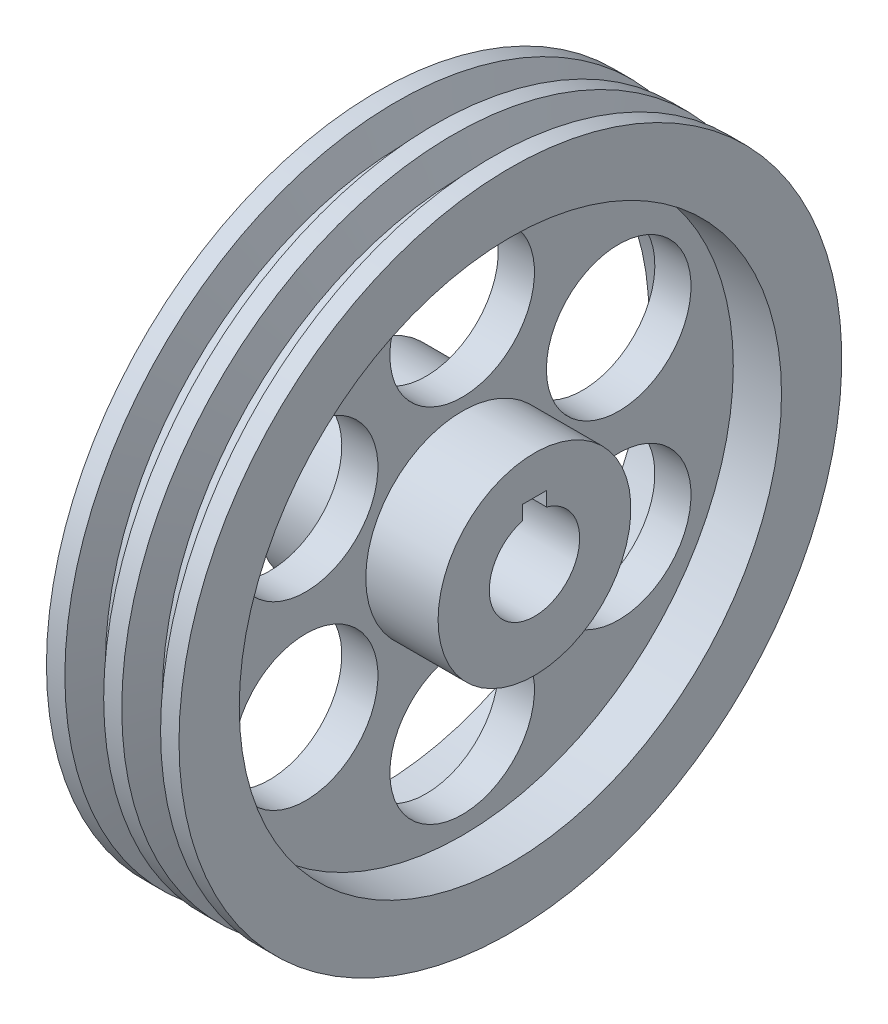
SolidWorks part; units mm, degrees
ref_plane "前视基准面" through (0, 0, 0) normal (0, 0, 1) x (1, 0, 0)
ref_plane "上视基准面" through (0, 0, 0) normal (0, 1, 0) x (1, 0, 0)
ref_plane "右视基准面" through (0, 0, 0) normal (1, 0, 0) x (0, 0, -1)
other "Configuration Table"
sketch "草图5" plane through (0, 0, 0) normal (0, 0, 1) x (1, 0, 0)
  line L0 (-49.9228, 0) -> (64.5367, 0) construction
  line L1 (-15.9481, 7.5) -> (14.0519, 7.5)
  line L2 (14.0519, 7.5) -> (14.0519, 16)
  line L3 (14.0519, 16) -> (2.0519, 16)
  line L4 (2.0519, 16) -> (2.0519, 45)
  line L5 (2.0519, 45) -> (10.0519, 45)
  line L6 (10.0519, 45) -> (10.0519, 55)
  line L7 (10.0519, 55) -> (6.9951, 55)
  line L8 (6.9951, 55) -> (5.2735, 50)
  line L9 (5.2735, 50) -> (2.2735, 50)
  line L10 (2.2735, 50) -> (0.5519, 55)
  line L11 (0.5519, 55) -> (-2.4481, 55)
  line L12 (-0.9481, 55) -> (-0.9481, 7.5) construction
  line L13 (-4.1698, 50) -> (-2.4481, 55)
  line L14 (-7.1698, 50) -> (-4.1698, 50)
  line L15 (-8.8914, 55) -> (-7.1698, 50)
  line L16 (-11.9481, 55) -> (-8.8914, 55)
  line L17 (-11.9481, 45) -> (-11.9481, 55)
  line L18 (-3.9481, 45) -> (-11.9481, 45)
  line L19 (-3.9481, 16) -> (-3.9481, 45)
  line L20 (-15.9481, 16) -> (-3.9481, 16)
  line L21 (-15.9481, 7.5) -> (-15.9481, 16)
  line L22 (3.7735, 50) -> (3.7735, 48.9551) construction
  line L23 (0, 0) -> (0, 7.5) construction
  dimension "D1" = 30
  dimension "D3" = 38
  dimension "D4" = 6
  dimension "D5" = 22
  dimension "D6" = 3
  dimension "D7" = 55
  dimension "D8" = 50
  dimension "D9" = 45
  dimension "D10" = 7.5
  dimension "D11" = 16
  dimension "D12" = 0.9481
revolve "旋转4" add sketch "草图5" angle 360 about L0
sketch "草图6" plane through (14.0519, 0, 0) normal (1, 0, 0) x (0, 0, -1)
  line L1 (-2, 9.6) -> (2, 9.6)
  line L2 (-2, 9.6) -> (-2, 0)
  line L3 (-2, 0) -> (2, 0)
  line L4 (2, 9.6) -> (2, 0)
  line L5 (-2, 9.6) -> (2, 0) construction
  line L6 (-2, 0) -> (2, 9.6) construction
  point P0 (0, 4.8)
  dimension "D1" = 9.6
  dimension "D2" = 4
  dimension "D3" = 0
  dimension "D4" = 0
extrude "切除-拉伸4" cut sketch "草图6" against normal through all
ref_axis "基准轴2" through (0, 0, 0) along (-1, 0, 0)
sketch "草图7" plane through (-3.9481, 0, 0) normal (-1, 0, 0) x (0, 0, 1)
  line L0 (0, 0) -> (0, 57.2869) construction
  circle A0 centre (0, 30) radius 12
  dimension "D1" = 24
  dimension "D2" = 30
extrude "切除-拉伸7" cut sketch "草图7" against normal through all
pattern_circular "阵列(圆周)2" count 6 over 360 about axis through (0, 0, 0) along (-1, 0, 0) of "切除-拉伸7"
